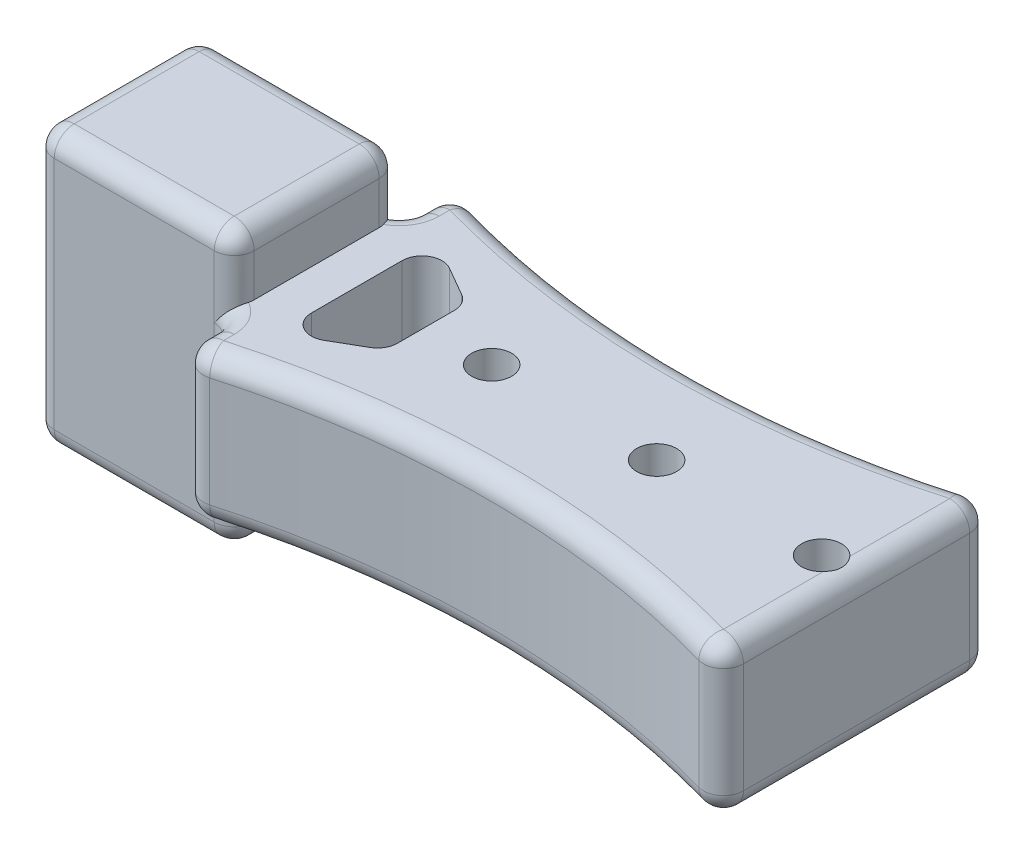
SolidWorks part; units mm, degrees
ref_plane "Front Plane" through (0, 0, 0) normal (0, 0, 1) x (1, 0, 0)
ref_plane "Top Plane" through (0, 0, 0) normal (0, 1, 0) x (1, 0, 0)
ref_plane "Right Plane" through (0, 0, 0) normal (1, 0, 0) x (0, 0, -1)
sketch "Sketch1" plane through (0, 0, 0) normal (0, 1, 0) x (1, 0, 0)
  line L1 (0, 0) -> (54, 0)
  line L2 (0, 0) -> (0, 40)
  line L3 (0, 40) -> (54, 40)
  line L4 (54, 0) -> (54, 40)
  circle A0 centre (34, 20) radius 2
  circle A1 centre (17.5, 20) radius 2
  circle A2 centre (50.5, 20) radius 2
  dimension "D3" = 4
  dimension "D4" = 4
  dimension "D5" = 4
  dimension "D1" = 54
  dimension "D2" = 40
  dimension "D6" = 3.5
  dimension "D7" = 20
  dimension "D8" = 16.5
  dimension "D9" = 16.5
extrude "Boss-Extrude1" add sketch "Sketch1" along normal blind 15
sketch "Sketch2" plane through (0, 0, 0) normal (-1, 0, 0) x (0, 0, 1)
  line L1 (-28.25, -6.25) -> (-11.75, -6.25)
  line L2 (-28.25, -6.25) -> (-28.25, 21.25)
  line L3 (-28.25, 21.25) -> (-11.75, 21.25)
  line L4 (-11.75, -6.25) -> (-11.75, 21.25)
  line L5 (-40, 0) -> (0, 0) construction
  line L6 (-40, 15) -> (-40, 0) construction
  dimension "D1" = 27.5
  dimension "D2" = 6.25
  dimension "D3" = 11.75
  dimension "D4" = 16.5
extrude "Boss-Extrude2" add sketch "Sketch2" along normal blind 20
sketch "Sketch3" plane through (-20, 0, 0) normal (-1, 0, 0) x (0, 0, 1)
  line L1 (-25.75, 18.75) -> (-14.25, 18.75)
  line L2 (-25.75, 18.75) -> (-25.75, -3.85)
  line L3 (-25.75, -3.85) -> (-14.25, -3.85)
  line L4 (-14.25, 18.75) -> (-14.25, -3.85)
  line L8 (-11.75, 21.25) -> (-28.25, 21.25) construction
  line L9 (-28.25, 21.25) -> (-28.25, -6.25) construction
  dimension "D1" = 11.5
  dimension "D2" = 22.6
  dimension "D3" = 2.5
  dimension "D4" = 2.5
extrude "Cut-Extrude1" cut sketch "Sketch3" against normal blind 17
sketch "Sketch4" plane through (0, 0, 0) normal (1, 0, 0) x (0, 0, -1)
  line L0 (28.25, -6.25) -> (11.75, -6.25) construction
  line L1 (15.75, -0.75) -> (24.25, -0.75)
  line L2 (15.75, -0.75) -> (15.75, -3.75)
  line L3 (15.75, -3.75) -> (24.25, -3.75)
  line L4 (24.25, -0.75) -> (24.25, -3.75)
  line L5 (11.75, -6.25) -> (11.75, 0) construction
  line L6 (28.25, 0) -> (28.25, -6.25) construction
  dimension "D1" = 2.5
  dimension "D2" = 3
  dimension "D3" = 4
  dimension "D4" = 4
extrude "Cut-Extrude2" cut sketch "Sketch4" against normal blind 22.5
fillet "Fillet1" radius 2 1 edges at (0, 0, -20)
fillet "Fillet2" radius 2 10 edges at (-10, 21.25, -11.75) (-10, 21.25, -28.25) (-10, -6.25, -28.25) (-10, -6.25, -11.75) (54, 7.5, -40) (0, 7.5, -40) (0, 7.5, -28.25) (0, 7.5, -11.75) (0, 7.5, 0) (54, 7.5, 0)
fillet "Fillet3" radius 2 8 edges at (-20, -5.6642, -27.6642) (-20, 7.5, -28.25) (-20, 20.6642, -27.6642) (-20, 21.25, -20) (-20, 20.6642, -12.3358) (-20, 7.5, -11.75) (-20, -5.6642, -12.3358) (-20, -6.25, -20)
fillet "Fillet4" radius 2 12 edges at (0.5858, -0.5858, -28.25) (0, -3.125, -28.25) (0, -5.6642, -27.6642) (0.5858, -0.5858, -11.75) (0, -3.125, -11.75) (0, -5.6642, -12.3358) (0, 17.125, -11.75) (0, 20.6642, -12.3358) (0, 17.125, -28.25) (0, 20.6642, -27.6642) (0, -6.25, -20) (0, 21.25, -20)
sketch "Sketch5" plane through (0, 15, 0) normal (0, 1, 0) x (1, 0, 0)
  line L0 (0, 38) -> (0, 30.25) construction
  line L1 (54, 2) -> (54, 38) construction
  line L2 (52, 40) -> (2, 40) construction
  line L4 (0, 9.75) -> (0, 2) construction
  line L5 (2, 0) -> (52, 0) construction
  line L6 (0, 6) -> (0, 0)
  line L7 (0, 0) -> (54, 0)
  line L8 (54, 0) -> (54, 6)
  line L9 (0, 34) -> (0, 40.0732)
  line L10 (0, 40.0732) -> (54, 40.0732)
  line L11 (54, 40.0732) -> (54, 34)
  arc A0 (0, 34) -> (54, 34) centre (27, 119.8545) ccw
  arc A1 (0, 6) -> (54, 6) centre (27, -79.8545) cw
  dimension "D3" = 90
  dimension "D6" = 90
  dimension "D1" = 6
  dimension "D2" = 6
  dimension "D4" = 6
  dimension "D5" = 6
extrude "Cut-Extrude3" cut sketch "Sketch5" against normal blind 30
fillet "Fillet5" radius 2 18 edges at (0, 0, -7.875) (0, 15, -32.125) (0, 0, -32.125) (0, 15, -7.875) (-0.5858, 0, -11.1642) (54, 0, -20) (54, 15, -20) (-0.5858, 15, -28.8358) (-0.5858, 0, -28.8358) (27, 0, -10.1455) (27, 0, -29.8545) (27, 15, -29.8545) (27, 15, -10.1455) (-0.5858, 15, -11.1642) (0, 7.5, -6) (54, 7.5, -6) (54, 7.5, -34) (0, 7.5, -34)
sketch "Sketch6" plane through (0, 15, 0) normal (0, 1, 0) x (1, 0, 0)
  line L0 (4, 27.9986) -> (4, 11.9986)
  line L1 (4, 11.9986) -> (10.9282, 15.9986)
  line L2 (10.9282, 15.9986) -> (10.9282, 23.9986)
  line L3 (10.9282, 23.9986) -> (4, 27.9986)
  dimension "D1" = 16
  dimension "D2" = 8
  dimension "D3" = 8
  dimension "D4" = 8
  dimension "D5" = 4
  dimension "D6" = 3.315
extrude "Cut-Extrude4" cut sketch "Sketch6" against normal blind 30
fillet "Fillet6" radius 2 4 edges at (4, 7.5, -11.9986) (10.9282, 7.5, -15.9986) (10.9282, 7.5, -23.9986) (4, 7.5, -27.9986)
